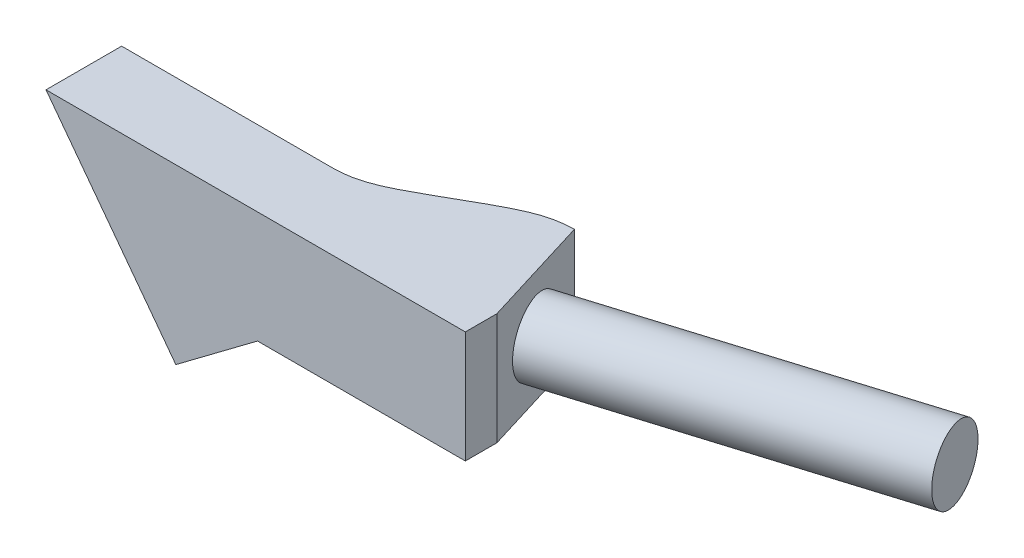
SolidWorks part; units mm, degrees
material "Custom Plastic"
ref_plane "X-Y Datum" through (0, 0, 0) normal (0, 0, 1) x (1, 0, 0)
ref_plane "X-Z Datum" through (0, 0, 0) normal (0, 1, 0) x (1, 0, 0)
ref_plane "Y-Z Datum" through (0, 0, 0) normal (1, 0, 0) x (0, 0, -1)
sketch "Sketch1" plane through (0, 0, 0) normal (0, 0, 1) x (1, 0, 0)
  line L1 (-38.1, -12.7) -> (38.1, -12.7)
  line L2 (-38.1, -12.7) -> (-38.1, 12.7)
  line L3 (-38.1, 12.7) -> (38.1, 12.7)
  line L4 (38.1, -12.7) -> (38.1, 12.7)
  line L5 (-38.1, -12.7) -> (38.1, 12.7) construction
  line L6 (-38.1, 12.7) -> (38.1, -12.7) construction
  point P0 (0, 0)
  dimension "D1" = 25.4
  dimension "D2" = 76.2
extrude "Boss-Extrude1" add sketch "Sketch1" along normal blind 12.7 and the other way blind 12.7
sketch "Sketch2" plane through (0, -12.7, 0) normal (0, -1, 0) x (1, 0, 0)
  line L0 (30.3, -12.7) -> (38.1, 12.7)
  line L1 (-38.1, -12.7) -> (38.1, -12.7) construction
  line L2 (30.3, -12.7) -> (38.1, -12.7)
  line L3 (38.1, -12.7) -> (38.1, 12.7)
  line L4 (34.2, 0) -> (87.6682, -16.4194)
  line L5 (-38.1, 12.7) -> (38.1, 12.7) construction
  line L6 (-9.1056, 2.7) -> (-38.1, 2.7)
  line L7 (-38.1, -12.7) -> (-38.1, 12.7) construction
  line L8 (30.3, -12.7) -> (13.797, -12.7)
  line L9 (-38.1, -12.7) -> (-38.1, 2.7)
  line L10 (30.3, -12.7) -> (-38.1, -12.7)
  spline S0 degree 3 poles (30.3, -12.7) (25.4668, -12.7) (16.7078, -8.7882) (4.4492, -1.2118) (-4.1851, 2.7) (-9.1056, 2.7) knots 0 0 0 0 0.311689 0.688311 1 1 1 1
  point P7 (34.2, 0)
  line M5 (38.1, -12.7) -> (38.1, 12.7)
  line M8 (-38.1, -12.7) -> (38.1, -12.7)
  dimension "D1" = 17.071
  dimension "D2" = 28.9944
  dimension "D3" = 10
  dimension "D4" = 3.81
  dimension "D5" = 3.81
  dimension "D6" = 12.7
  dimension "D7" = 12.7
extrude "Cut-Extrude1" cut sketch "Sketch2" against normal through all contours L4 L0 M8 M5 | L0 L4 L3 | L10 L9 L6 S0 region at (35.0104, -12.7, -7.2716) region at (36.8, -12.7, 3.8341)
sketch "Sketch4" plane through (31.2528, 0, -9.5973) normal (0.9559, 0, -0.2936) x (-0.2936, 0, -0.9559)
  line L1 (-23.325, -12.7) -> (-23.325, 12.7) construction
  circle A0 centre (-10.0397, 0) radius 7.9375
  dimension "D1" = 15.875
  dimension "D2" = 13.2853
extrude "Boss-Extrude2" add sketch "Sketch4" along normal blind 76.2
sketch "Sketch5" plane through (0, 0, 2.7) normal (0, 0, -1) x (-1, 0, 0)
  line L0 (38.1, -12.7) -> (57.1506, 12.7)
  line L1 (57.1506, 12.7) -> (38.1, 12.7)
  line L2 (0, 0) -> (72.4016, 0) construction
  line L3 (72.4016, 0) -> (-7.6416, 60.0343) construction
  line L4 (38.1, 12.7) -> (38.1, -12.7)
  line L5 (9.1056, -12.7) -> (27.6616, -26.6174)
  line L6 (27.6616, -26.6174) -> (38.1, -12.7)
  line L7 (38.1, -12.7) -> (9.1056, -12.7)
  line M4 (9.1056, -12.7) -> (38.1, -12.7)
  line M5 (38.1, -12.7) -> (38.1, 12.7)
  dimension "D1" = 36.871
extrude "Boss-Extrude3" add sketch "Sketch5" against normal up to surface (10 mm away) contours L5 L6 M4 | L0 L1 M5 region at (-44.4502, 4.2333, 2.7) region at (-24.9558, -17.3391, 2.7) up to face at (0, 0, 12.7)
sketch "Sketch6" [suppressed] plane through (0, 0, 2.7) normal (0, 0, -1) x (-1, 0, 0)
  line L0 (0, 0) -> (115.4941, 0) construction
  line L1 (115.4941, 0) -> (-57.8809, -130.0354) construction
  line L2 (38.1, 19.05) -> (66.6759, -19.05)
  line L3 (66.6759, -19.05) -> (38.1, -19.05)
  line L4 (38.1, -19.05) -> (38.1, 19.05)
  line L5 (38.1, 19.05) -> (27.6616, 32.9674)
  line L6 (27.6616, 32.9674) -> (9.1056, 19.05)
  line L7 (9.1056, 19.05) -> (38.1, 19.05) construction
  line L8 (9.1056, 19.05) -> (38.1, 19.05)
  line M5 (38.1, -19.05) -> (38.1, 19.05)
  line M6 (38.1, 19.05) -> (9.1056, 19.05)
  dimension "D1" = 36.871
extrude "Boss-Extrude4" [suppressed] add sketch "Sketch6" against normal up to surface (10 mm away) contours L3 L2 M5 | L5 L6 M6
sketch "Sketch7" plane through (0, 0, 12.7) normal (0, 0, 1) x (1, 0, 0)
  line L5 (-57.1506, 12.7) -> (-27.6616, -26.6174)
  line L6 (-57.1506, 12.7) -> (-27.6616, -26.6174)
  line L7 (-27.6616, -26.6174) -> (-9.1056, -12.7)
  line L8 (-27.6616, -26.6174) -> (-9.1056, -12.7)
  line L10 (38.1, -12.7) -> (38.1, 12.7)
  line L11 (38.1, 12.7) -> (-57.1506, 12.7)
  line L14 (-9.1056, -12.7) -> (38.1, -12.7)
  line L15 (38.1, -12.7) -> (38.1, 12.7)
  line L16 (38.1, 12.7) -> (-57.1506, 12.7)
  line L19 (-9.1056, -12.7) -> (38.1, -12.7)
  dimension "D1" = 0
extrude "Boss-Extrude5" add sketch "Sketch7" along normal blind 7.1782 contours L15 L16 L6 L8 L19
